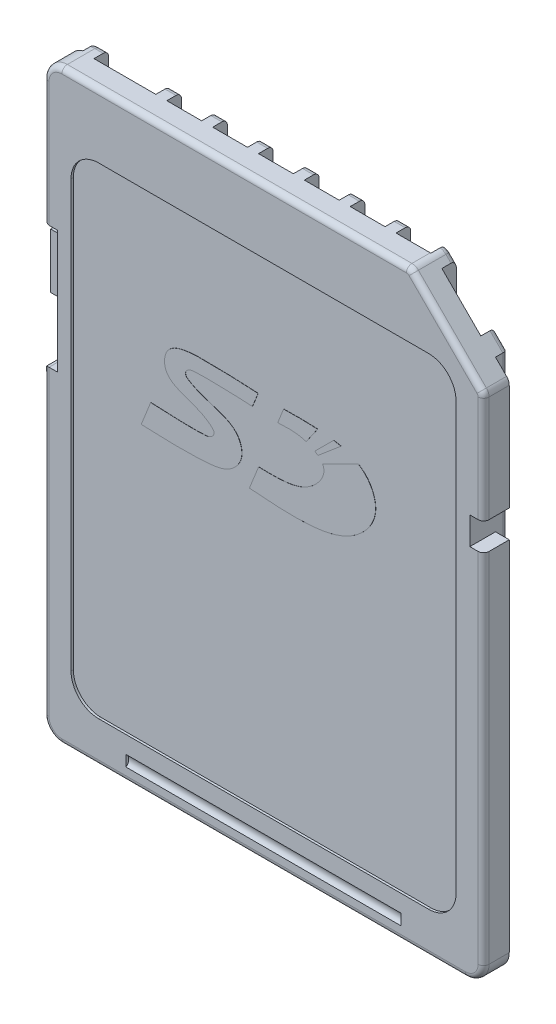
SolidWorks part; units mm, degrees
ref_plane "Front" through (0, 0, 0) normal (0, 0, 1) x (1, 0, 0)
ref_plane "Top" through (0, 0, 0) normal (0, 1, 0) x (1, 0, 0)
ref_plane "Right" through (0, 0, 0) normal (1, 0, 0) x (0, 0, -1)
sketch "Sketch1" plane through (0, 0, 0) normal (0, 0, 1) x (1, 0, 0)
  line L0 (0, 0) -> (0, -32) construction
  line L1 (-12, 0) -> (12, 0)
  line L2 (-12, 0) -> (-12, -32)
  line L3 (-12, -32) -> (12, -32)
  line L4 (12, 0) -> (12, -32)
  dimension "D1" = 24
  dimension "D2" = 32
extrude "Main Body" add sketch "Sketch1" along normal mid plane 2.1
chamfer "Index Corner" distance 4 angle 45 1 edges at (12, 0, 0)
sketch "Sketch2" plane through (0, 0, 1.05) normal (0, 0, 1) x (1, 0, 0)
  line L0 (12, -32) -> (12, -4) construction
  line L1 (12, -10) -> (11.25, -10)
  line L2 (12, -10) -> (12, -11.5)
  line L3 (12, -11.5) -> (11.25, -11.5)
  line L4 (11.25, -10) -> (11.25, -11.5)
  line L5 (-12, 0) -> (-12, -32) construction
  line L6 (-12, -7.8) -> (-11.25, -7.8)
  line L7 (-12, -7.8) -> (-12, -14.5)
  line L8 (-12, -14.5) -> (-11.25, -14.5)
  line L9 (-11.25, -7.8) -> (-11.25, -14.5)
  line L10 (8, 0) -> (-12, 0) construction
  dimension "D1" = 1.5
  dimension "D2" = 0.75
  dimension "D3" = 10
  dimension "D4" = 6.7
  dimension "D5" = 0.75
  dimension "D6" = 7.8
extrude "Lock Tab Cutout" cut sketch "Sketch2" against normal through all
sketch "Sketch3" plane through (0, -32, 0) normal (0, -1, 0) x (1, 0, 0)
  line L0 (0, 0) -> (0, -3.3888) construction
  line L1 (-12, -1.05) -> (-11.25, -1.05)
  line L2 (-12, -1.05) -> (-12, -0.35)
  line L3 (-12, -0.35) -> (-11.25, -0.35)
  line L4 (-11.25, -1.05) -> (-11.25, -0.35)
  line L5 (12, -1.05) -> (11.25, -1.05)
  line L6 (12, -1.05) -> (12, -0.35)
  line L7 (12, -0.35) -> (11.25, -0.35)
  line L8 (11.25, -1.05) -> (11.25, -0.35)
  line L9 (-12, 1.05) -> (12, 1.05) construction
  dimension "D1" = 22.5
  dimension "D2" = 1.4
extrude "Indexing Notch" cut sketch "Sketch3" against normal through all
sketch "Sketch4" plane through (0, 0, -1.05) normal (0, 0, -1) x (-1, 0, 0)
  line L1 (-8.125, 7.1794) -> (-8.125, -12.3462) construction
  line L2 (-5.625, 7.1794) -> (-5.625, -12.3462) construction
  line L3 (-3.125, 7.1794) -> (-3.125, -12.3462) construction
  line L4 (-0.625, 7.1794) -> (-0.625, -12.3462) construction
  line L5 (1.875, 7.1794) -> (1.875, -12.3462) construction
  line L6 (4.375, 7.1794) -> (4.375, -12.3462) construction
  line L7 (6.875, 7.1794) -> (6.875, -12.3462) construction
  line L8 (-8, 0) -> (11.25, 0) construction
  line L9 (-7.825, 0) -> (-5.925, 0)
  line L10 (-7.825, 0) -> (-7.825, -5.65)
  line L11 (-7.825, -5.65) -> (-5.925, -5.65)
  line L12 (-5.925, 0) -> (-5.925, -5.65)
  line L13 (11.25, -32) -> (11.25, 0) construction
  line L14 (-5.325, 0) -> (-3.425, 0)
  line L15 (-5.325, 0) -> (-5.325, -5.65)
  line L16 (-5.325, -5.65) -> (-3.425, -5.65)
  line L17 (-3.425, 0) -> (-3.425, -5.65)
  line L18 (-2.825, 0) -> (-0.925, 0)
  line L19 (-2.825, 0) -> (-2.825, -5.65)
  line L20 (-2.825, -5.65) -> (-0.925, -5.65)
  line L21 (-0.925, 0) -> (-0.925, -5.65)
  line L22 (-0.325, 0) -> (1.575, 0)
  line L23 (-0.325, 0) -> (-0.325, -5.65)
  line L24 (-0.325, -5.65) -> (1.575, -5.65)
  line L25 (-10.55, 0) -> (-8.425, 0)
  line L26 (-10.55, 0) -> (-10.55, -7.65)
  line L27 (-10.55, -7.65) -> (-8.425, -7.65)
  line L28 (-8.425, 0) -> (-8.425, -7.65)
  line L29 (-11.25, -3.25) -> (-11.25, -32) construction
  line L31 (1.575, 0) -> (1.575, -5.65)
  line L32 (2.175, 0) -> (4.075, 0)
  line L33 (2.175, 0) -> (2.175, -5.65)
  line L34 (2.175, -5.65) -> (4.075, -5.65)
  line L35 (4.075, 0) -> (4.075, -5.65)
  line L36 (0, -32) -> (0, 7.767) construction
  line L37 (11.25, -32) -> (-11.25, -32) construction
  line L38 (4.675, 0) -> (6.575, 0)
  line L39 (4.675, 0) -> (4.675, -5.65)
  line L40 (4.675, -5.65) -> (6.575, -5.65)
  line L41 (6.575, 0) -> (6.575, -5.65)
  line L42 (7.175, 0) -> (10.55, 0)
  line L43 (7.175, 0) -> (7.175, -5.65)
  line L44 (7.175, -5.65) -> (10.55, -5.65)
  line L45 (10.55, 0) -> (10.55, -5.65)
  dimension "D1" = 8.125
  dimension "D2" = 2.5
  dimension "D3" = 0.6
  dimension "D4" = 0.7
  dimension "D5" = 0.6
  dimension "D6" = 0.6
  dimension "D7" = 7.65
  dimension "D8" = 0.6
  dimension "D9" = 0.6
  dimension "D10" = 0.6
  dimension "D11" = 5.65
  dimension "D12" = 0.6
  dimension "D13" = 0.7
extrude "Contact Cutouts" cut sketch "Sketch4" against normal blind 0.8
draft "Draft1" type of draft neutral plane draft angle 25 faces to draft 7 face at (6.875, -5.65, -0.65) face at (4.375, -5.65, -0.65) face at (1.875, -5.65, -0.65) face at (-0.625, -5.65, -0.65) face at (-3.125, -5.65, -0.65) face at (-5.625, -5.65, -0.65) face at (-8.8625, -5.65, -0.65) neutral plane through (-7.175, 0, -0.25) neutral plane normal (0, 0, -1) parameters "D1"=25
draft "Draft2" type of draft neutral plane draft angle 25 faces to draft 1 face at (9.4875, -7.65, -0.65) neutral plane through (10.55, -7.65, -0.25) neutral plane normal (0, 0, -1) parameters "D1"=25
fillet "Fillet3" radius 0.5 4 edges at (11.25, -32, -0.7) (-11.25, -32, -0.7) (12, -4, 0.35) (8, 0, 0)
fillet "Fillet1" radius 1 3 edges at (12, -32, 0.35) (-12, -32, 0.35) (-12, 0, 0.35)
fillet "Fillet4" radius 0.3 25 edges at (-12, -14.5, 0.35) (-12, -7.8, 0.35) (12, -7.1036, 1.05) (11.9619, -4.0158, 1.05) (10, -2, 1.05) (7.9842, -0.0381, 1.05) (-1.6036, 0, 1.05) (-12, -4.4, 1.05) (-12, -22.75, 1.05) (-11.7071, -31.7071, 1.05) (12, -21.25, 1.05) (11.7071, -31.7071, 1.05) (-11.7071, -0.2929, 1.05) (0, -32, 1.05) (8.2857, -0.2857, -1.05) (10.9, -2.9, -1.05) (7.999, -0.0444, -1.05) (5.625, 0, -1.05) (3.125, 0, -1.05) (0.625, 0, -1.05) (-1.875, 0, -1.05) (-4.375, 0, -1.05) (-6.875, 0, -1.05) (-11.126, -0.008, -1.05) (-10.775, 0, -1.05)
sketch "Sketch5" plane through (0, 0, 1.05) normal (0, 0, 1) x (1, 0, 0)
  line L0 (-11, -32) -> (11, -32) construction
  line L1 (-9, -3.5) -> (9, -3.5)
  line L2 (-10.5, -5) -> (-10.5, -28.25)
  line L3 (-9, -29.75) -> (9, -29.75)
  line L4 (10.5, -5) -> (10.5, -28.25)
  line L5 (12, -31) -> (12, -11.5) construction
  line L6 (-12, -14.5) -> (-12, -31) construction
  line L8 (-11, 0) -> (7.7929, 0) construction
  arc A0 (-9, -3.5) -> (-10.5, -5) centre (-9, -5) ccw
  arc A1 (9, -3.5) -> (10.5, -5) centre (9, -5) cw
  arc A2 (9, -29.75) -> (10.5, -28.25) centre (9, -28.25) ccw
  arc A3 (-10.5, -28.25) -> (-9, -29.75) centre (-9, -28.25) ccw
  dimension "D5" = 1.5
  dimension "D1" = 2.25
  dimension "D2" = 1.5
  dimension "D3" = 1.5
  dimension "D4" = 3.5
extrude "Label" cut sketch "Sketch5" against normal blind 0.127
sketch "Sketch6" plane through (-11.25, 0, 0) normal (-1, 0, 0) x (0, 0, 1)
  line L0 (-0.35, -3.25) -> (-0.35, -10) construction
  line L1 (-0.35, -7.8) -> (0.3, -7.8)
  line L2 (-0.35, -7.8) -> (-0.35, -14.5)
  line L3 (-0.35, -14.5) -> (0.3, -14.5)
  line L4 (0.3, -7.8) -> (0.3, -14.5)
  line L5 (-0.35, -14.5) -> (1.05, -14.5) construction
  line L6 (-0.35, -7.8) -> (1.05, -7.8) construction
  line L7 (1.05, -14.5) -> (1.05, -7.8) construction
  dimension "D1" = 0.75
extrude "Slide Lock Notch" cut sketch "Sketch6" against normal blind 1
ref_plane "Plane1" through (0, -8.054, 0) normal (0, -1, 0) x (1, 0, 0)
sketch "Sketch7" plane through (0, -8.054, 0) normal (0, -1, 0) x (1, 0, 0)
  line L0 (-10.25, 0.3) -> (-11.25, 0.3) construction
  line L1 (-10.25, 0.3) -> (-10.25, -0.35) construction
  line L2 (-10.25, -0.35) -> (-11.25, -0.35) construction
  line L3 (-10.25, 0.3) -> (-11.377, 0.3)
  line L4 (-10.25, 0.3) -> (-10.25, -0.35)
  line L5 (-10.25, -0.35) -> (-11.873, -0.35)
  line L6 (-11.873, -0.35) -> (-11.873, 0.923)
  line L7 (-11.873, 0.923) -> (-11.377, 0.923)
  line L8 (-11.377, 0.923) -> (-11.377, 0.3)
  line L9 (-11.25, 1.05) -> (-11.7, 1.05) construction
  line L10 (-12, -0.35) -> (-12, 1.05) construction
  line L11 (-11.25, 0.3) -> (-11.25, 1.05) construction
  dimension "D1" = 0.127
  dimension "D2" = 0.127
  dimension "D3" = 0.127
extrude "Lock Slide Tab" add sketch "Sketch7" along normal blind 3
chamfer "Chamfer2" distance 0.127 angle 45 4 edges at (-11.873, -11.054, 0.2865) (-11.873, -8.054, 0.2865) (-11.873, -9.554, -0.35) (-11.873, -9.554, 0.923)
fillet "Fillet5" radius 0.3 3 edges at (0, -32, -1.05) (11.25, -17.5871, -1.05) (-11.25, -15.9231, -1.05)
sketch "Sketch8" plane through (0, 0, -0.25) normal (0, 0, -1) x (-1, 0, 0)
  line L0 (-9.4875, -7.65) -> (-9.4875, 0) construction
  line L1 (-8.7875, -4) -> (-9.7375, -4)
  line L2 (-8.7875, -4) -> (-8.7875, -7)
  line L3 (-8.7875, -7) -> (-10.1875, -7)
  line L4 (-10.1875, -4.45) -> (-10.1875, -7)
  line L5 (-10.55, -7.65) -> (-8.425, -7.65) construction
  line L6 (-6.875, -5.65) -> (-6.875, 0) construction
  line L7 (-7.825, -5.65) -> (-5.925, -5.65) construction
  line L8 (-4.375, -5.65) -> (-4.375, 0) construction
  line L9 (-5.325, -5.65) -> (-3.425, -5.65) construction
  line L10 (-1.875, -5.65) -> (-1.875, 0) construction
  line L11 (-2.825, -5.65) -> (-0.925, -5.65) construction
  line L12 (0.625, -5.65) -> (0.625, 0) construction
  line L13 (-0.325, -5.65) -> (1.575, -5.65) construction
  line L14 (3.125, -5.65) -> (3.125, 0) construction
  line L15 (2.175, -5.65) -> (4.075, -5.65) construction
  line L16 (5.625, -5.65) -> (5.625, 0) construction
  line L17 (4.675, -5.65) -> (6.575, -5.65) construction
  line L18 (-10.1875, -4.45) -> (-9.7375, -4)
  line L19 (-5.925, 0) -> (-7.7929, 0) construction
  line L20 (-3.425, 0) -> (-5.325, 0) construction
  line L21 (-7.575, -1.6) -> (-6.175, -1.6)
  line L22 (-7.575, -1.6) -> (-7.575, -5)
  line L23 (-7.575, -5) -> (-6.175, -5)
  line L24 (-6.175, -1.6) -> (-6.175, -5)
  line L25 (-5.075, -5) -> (-3.675, -5)
  line L26 (-5.075, -5) -> (-5.075, -1.6)
  line L27 (-5.075, -1.6) -> (-3.675, -1.6)
  line L28 (-3.675, -5) -> (-3.675, -1.6)
  line L29 (-2.575, -5) -> (-1.175, -5)
  line L30 (-2.575, -5) -> (-2.575, -1.4)
  line L31 (-2.575, -1.4) -> (-1.175, -1.4)
  line L32 (-1.175, -5) -> (-1.175, -1.4)
  line L33 (-0.075, -5) -> (1.325, -5)
  line L34 (-0.075, -5) -> (-0.075, -1.4)
  line L35 (-0.075, -1.4) -> (1.325, -1.4)
  line L36 (1.325, -5) -> (1.325, -1.4)
  line L37 (2.425, -5) -> (3.825, -5)
  line L38 (2.425, -5) -> (2.425, -1.6)
  line L39 (2.425, -1.6) -> (3.825, -1.6)
  line L40 (3.825, -5) -> (3.825, -1.6)
  line L41 (4.925, -5) -> (6.325, -5)
  line L42 (4.925, -5) -> (4.925, -1.6)
  line L43 (4.925, -1.6) -> (6.325, -1.6)
  line L44 (6.325, -5) -> (6.325, -1.6)
  line L45 (-0.925, 0) -> (-2.825, 0) construction
  line L46 (1.575, 0) -> (-0.325, 0) construction
  line L49 (4.075, 0) -> (2.175, 0) construction
  line L50 (6.575, 0) -> (4.675, 0) construction
  line L51 (7.175, -0.3) -> (7.175, -6.023) construction
  line L52 (7.675, -5) -> (8.775, -5)
  line L53 (7.675, -5) -> (7.675, -1.6)
  line L54 (7.675, -1.6) -> (8.775, -1.6)
  line L55 (8.775, -5) -> (8.775, -1.6)
  line L56 (9.025, -1.6) -> (9.925, -1.6)
  line L57 (9.025, -1.6) -> (9.025, -5)
  line L58 (9.025, -5) -> (9.925, -5)
  line L59 (9.925, -1.6) -> (9.925, -5)
  point P32 (-9.4875, -7)
  point P40 (-6.875, -5)
  point P61 (-4.375, -5)
  point P62 (-1.875, -5)
  point P63 (0.625, -5)
  point P64 (3.125, -5)
  point P65 (5.625, -5)
  dimension "D1" = 1.4
  dimension "D2" = 45
  dimension "D3" = 0.25
  dimension "D4" = 4
  dimension "D5" = 7
  dimension "D6" = 1.4
  dimension "D7" = 5
  dimension "D8" = 1.6
  dimension "D9" = 0.2
  dimension "D10" = 1.1
  dimension "D11" = 0.9
  dimension "D12" = 0.5
  dimension "D13" = 0.25
extrude "Contact Pads" add sketch "Sketch8" along normal up to surface (0.1 mm away) up to face at (-11.6855, -4.8131, -0.35)
sketch "Sketch9" plane through (0, 0, 0.923) normal (0, 0, 1) x (1, 0, 0)
  line L0 (-6.2724, -13.5134) -> (-6.7882, -14.803)
  line L1 (-0.416, -10.1548) -> (-0.7245, -10.9261)
  line L2 (0.9769, -10.1988) -> (0.6569, -10.999)
  line L3 (2.2054, -11.1193) -> (2.8323, -10.2173)
  line L4 (2.6781, -11.3337) -> (3.71, -10.3075)
  line L5 (2.8486, -11.4508) -> (4.1085, -10.3861)
  line L6 (3.1057, -11.7379) -> (5.0432, -10.7554)
  line L7 (-0.3889, -13.6135) -> (-0.8885, -14.8625)
  spline S0 degree 3 poles (-0.416, -10.1548) (-1.1309, -10.1159) (-1.8457, -10.0769) (-3.8317, -10.056) (-5.4519, -9.9554) (-5.5986, -12.3218) (-3.6941, -12.223) (-2.7473, -13.1983) (-2.9683, -13.5341) (-3.2371, -13.5757) (-4.1987, -13.6163) (-5.2355, -13.5649) (-6.2724, -13.5134) knots 0 0 0 0 0.184888 0.184888 0.410554 0.452271 0.688314 0.713033 0.734013 0.768579 0.768579 1 1 1 1
  spline S1 degree 3 poles (-6.7882, -14.803) (-5.6026, -14.8528) (-4.0119, -14.9196) (-1.9792, -14.6921) (-1.1349, -13.7038) (-1.5398, -12.3526) (-2.4217, -12.1234) (-3.4251, -11.7815) (-3.874, -11.6603) (-4.3292, -11.3325) (-4.4175, -11.193) (-4.2381, -10.8815) (-3.4043, -10.8203) (-2.7422, -10.8585) (-1.753, -10.8696) (-1.3042, -10.8927) (-0.7245, -10.9261) knots 0 0 0 0 0.256766 0.344487 0.429502 0.495963 0.609426 0.609426 0.712523 0.712523 0.728643 0.741601 0.781716 0.890531 0.890531 1 1 1 1
  spline S2 degree 3 poles (-0.8885, -14.8625) (0.1174, -14.9419) (2.048, -15.0944) (4.755, -14.6706) (6.3006, -12.7503) (5.7404, -11.2962) (5.2294, -10.8704) (5.0432, -10.7554) knots 0 0 0 0 0.216184 0.414924 0.566249 0.662816 0.710015 0.710015 0.710015 0.710015
  spline S3 degree 3 poles (-0.3889, -13.6135) (0.0689, -13.6241) (1.0654, -13.6472) (2.4715, -13.3412) (3.3064, -12.2054) (3.1282, -11.7787) (3.1057, -11.7379) knots 0 0 0 0 0.191941 0.417844 0.611311 0.632536 0.632536 0.632536 0.632536
  spline S4 degree 3 poles (2.2054, -11.1193) (1.6836, -10.9482) (1.1702, -10.9736) (0.6569, -10.999) knots 0.78093 0.78093 0.78093 0.78093 1 1 1 1
  spline S5 degree 3 poles (2.8323, -10.2173) (2.1903, -10.179) (1.5836, -10.1889) (0.9769, -10.1988) knots 0.867537 0.867537 0.867537 0.867537 1 1 1 1
  spline S6 degree 3 poles (4.1085, -10.3861) (3.9778, -10.3548) (3.8445, -10.329) (3.71, -10.3075) knots 0.780592 0.780592 0.780592 0.780592 0.808003 0.808003 0.808003 0.808003
  spline S7 degree 3 poles (2.8486, -11.4508) (2.7955, -11.409) (2.7382, -11.3699) (2.6781, -11.3337) knots 0.687307 0.687307 0.687307 0.687307 0.7141 0.7141 0.7141 0.7141
extrude "SD Logo" add sketch "Sketch9" along normal blind 0.01
sketch "Sketch10" plane through (0, 0, 0) normal (1, 0, 0) x (0, 0, -1)
  circle A0 centre (-1.2768, -30.988) radius 0.375
  dimension "D1" = 0.75
extrude "Finger Grab" cut sketch "Sketch10" against normal mid plane 15
